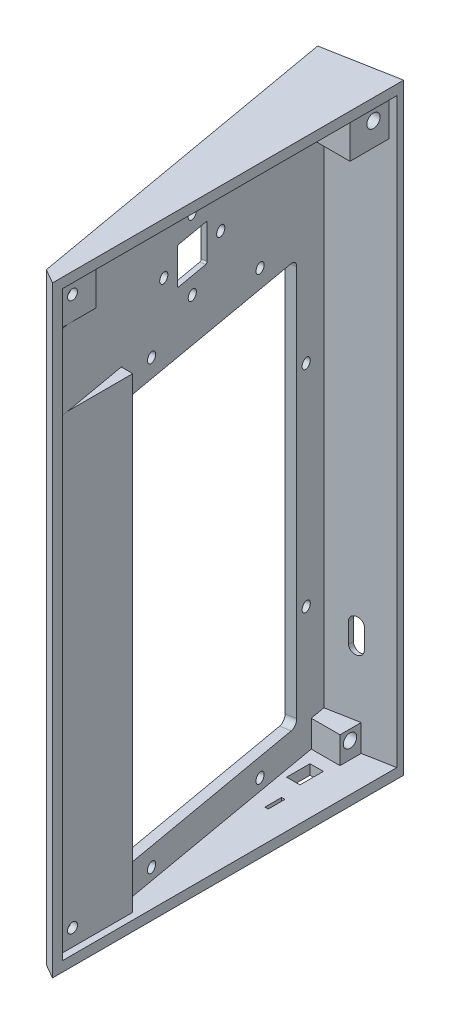
SolidWorks part; units mm, degrees
ref_plane "前视基准面" through (0, 0, 0) normal (0, 0, 1) x (1, 0, 0)
ref_plane "上视基准面" through (0, 0, 0) normal (0, 1, 0) x (1, 0, 0)
ref_plane "右视基准面" through (0, 0, 0) normal (1, 0, 0) x (0, 0, -1)
other "Configuration Table"
sketch "草图1" plane through (0, 0, 0) normal (0, 1, 0) x (1, 0, 0)
  line L0 (82.9035, -37.3993) -> (82.9035, -142.3993)
  line L1 (82.9035, -142.3993) -> (78.5734, -139.8993)
  line L2 (78.5734, -139.8993) -> (61.2086, -41.4185)
  line L3 (61.2086, -41.4185) -> (82.9035, -37.3993)
  dimension "D1" = 100
  dimension "D2" = 105
  dimension "D3" = 5
  dimension "D4" = 170
  dimension "D5" = 60
  dimension "D6" = 90.496
  dimension "D7" = 79.504
extrude "凸台-拉伸1" add sketch "草图1" along normal blind 180
sketch "草图5" plane through (52.2799, 0, -9.2184) normal (-0.9848, 0, 0.1736) x (0.1736, 0, 0.9848)
  line L0 (51.418, 180) -> (51.418, 0) construction
  line L1 (139.418, 12) -> (63.418, 12)
  line L2 (139.418, 12) -> (139.418, 133)
  line L3 (139.418, 133) -> (63.418, 133)
  line L4 (63.418, 12) -> (63.418, 133)
  line L5 (151.418, 180) -> (151.418, 0) construction
  line L6 (51.418, 0) -> (151.418, 0) construction
  dimension "D1" = 76
  dimension "D2" = 121
  dimension "D3" = 12
  dimension "D4" = 12
  dimension "D5" = 12
extrude "切除-拉伸2" cut sketch "草图5" against normal blind 2
sketch "草图7" plane through (82.9035, 0, 0) normal (1, 0, 0) x (0, 0, -1)
  line L8 (-139.3993, 3) -> (-40.3993, 3)
  line L9 (-40.3993, 3) -> (-40.3993, 177)
  line L10 (-40.3993, 177) -> (-139.3993, 177)
  line L11 (-139.3993, 177) -> (-139.3993, 3)
  line L12 (-139.3993, 3) -> (-40.3993, 3)
  line L13 (-40.3993, 3) -> (-40.3993, 177)
  line L14 (-40.3993, 177) -> (-139.3993, 177)
  line L15 (-139.3993, 177) -> (-139.3993, 3)
  dimension "D1" = 3
extrude "切除-拉伸3" cut sketch "草图7" against normal up to surface (19.8438 mm away) up to face at (71.8606, 72.5, 90.3116)
sketch "草图10" plane through (54.2496, 0, -9.5657) normal (0.9848, 0, -0.1736) x (-0.1736, 0, -0.9848)
  line L1 (-63.418, 12) -> (-59.918, 12) construction
  line L2 (-63.418, 12) -> (-63.418, 41) construction
  line L3 (-63.418, 41) -> (-59.918, 41) construction
  line L4 (-59.918, 12) -> (-59.918, 41) construction
  line L5 (-63.418, 133) -> (-59.918, 133) construction
  line L6 (-63.418, 133) -> (-63.418, 104) construction
  line L7 (-63.418, 104) -> (-59.918, 104) construction
  line L8 (-59.918, 133) -> (-59.918, 104) construction
  circle A0 centre (-59.918, 104) radius 1.5
  circle A1 centre (-59.918, 41) radius 1.5
  dimension "D1" = 29
  dimension "D2" = 29
  dimension "D3" = 3.5
  dimension "D4" = 3.5
extrude "切除-拉伸5" cut sketch "草图10" against normal blind 1
sketch "草图11" plane through (54.2496, 0, -9.5657) normal (0.9848, 0, -0.1736) x (-0.1736, 0, -0.9848)
  line L0 (-76.918, 6.5) -> (-116.918, 6.5) construction
  line L1 (-63.418, 133) -> (-76.918, 133) construction
  line L2 (-63.418, 133) -> (-63.418, 138.5) construction
  line L3 (-63.418, 138.5) -> (-76.918, 138.5) construction
  line L4 (-76.918, 133) -> (-76.918, 138.5) construction
  line L5 (-63.418, 12) -> (-76.918, 12) construction
  line L6 (-63.418, 12) -> (-63.418, 6.5) construction
  line L7 (-63.418, 6.5) -> (-76.918, 6.5) construction
  line L8 (-76.918, 12) -> (-76.918, 6.5) construction
  line L9 (-76.918, 138.5) -> (-116.918, 138.5) construction
  circle A0 centre (-116.918, 138.5) radius 1.5
  circle A1 centre (-76.918, 138.5) radius 1.5
  circle A2 centre (-116.918, 6.5) radius 1.5
  circle A3 centre (-76.918, 6.5) radius 1.5
  dimension "D1" = 13.5
  dimension "D2" = 5.5
  dimension "D3" = 13.5
  dimension "D4" = 5.5
  dimension "D5" = 40
  dimension "D6" = 40
extrude "切除-拉伸6" cut sketch "草图11" against normal blind 1
sketch "草图12" plane through (82.9035, 0, 0) normal (1, 0, 0) x (0, 0, -1)
  line L1 (-139.3993, 3) -> (-116.3993, 3)
  line L2 (-139.3993, 3) -> (-139.3993, 142.5)
  line L3 (-139.3993, 142.5) -> (-116.3993, 142.5)
  line L4 (-116.3993, 3) -> (-116.3993, 142.5)
  line L6 (-127.7343, 133) -> (-52.8889, 133) construction
  dimension "D1" = 9.5
  dimension "D2" = 23
extrude "凸台-拉伸3" add sketch "草图12" against normal up to surface (2.3874 mm away) up to face at (67.3458, 138.5, 64.7066)
sketch "草图13" plane through (54.2496, 0, -9.5657) normal (-0.9848, 0, 0.1736) x (0.1736, 0, 0.9848)
  line L4 (127.9081, 12) -> (139.418, 12)
  line L5 (139.418, 12) -> (139.418, 133)
  line L6 (139.418, 133) -> (127.9081, 133)
  line L7 (127.9081, 133) -> (127.9081, 12)
  line L8 (127.9081, 12) -> (139.418, 12)
  line L9 (139.418, 12) -> (139.418, 133)
  line L10 (139.418, 133) -> (127.9081, 133)
  line L11 (127.9081, 133) -> (127.9081, 12)
  dimension "D1" = 0
extrude "切除-拉伸7" cut sketch "草图13" against normal blind 2
sketch "草图14" plane through (52.2799, 0, -9.2184) normal (-0.9848, 0, 0.1736) x (0.1736, 0, 0.9848)
  line L0 (51.418, 180) -> (51.418, 0) construction
  line L1 (96.418, 151) -> (107.418, 151)
  line L2 (96.418, 151) -> (96.418, 162)
  line L3 (96.418, 162) -> (107.418, 162)
  line L4 (107.418, 151) -> (107.418, 162)
  line L5 (139.418, 133) -> (63.418, 133) construction
  line L6 (51.418, 180) -> (151.418, 180) construction
  dimension "D1" = 11
  dimension "D2" = 11
  dimension "D3" = 45
  dimension "D4" = 18
  dimension "D5" = 18
extrude "切除-拉伸8" cut sketch "草图14" against normal blind 2
sketch "草图17" plane through (9.4497, 0, 51.0074) normal (-0.1822, 0, -0.9833) x (-0.9833, 0, 0.1822)
  line L1 (-74.7037, 180) -> (-52.6396, 180)
  line L2 (-74.7037, 180) -> (-74.7037, 0)
  line L3 (-74.7037, 0) -> (-52.6396, 0)
  line L4 (-52.6396, 180) -> (-52.6396, 0)
extrude "凸台-拉伸9" add sketch "草图17" against normal blind 2
sketch "草图18" plane through (0, 0, 0) normal (0, -1, 0) x (1, 0, 0)
  line L0 (82.9035, 39.4333) -> (82.9035, 37.3993)
  line L1 (83.2679, 39.3658) -> (82.9035, 39.4333) construction
  line L2 (83.2679, 39.3658) -> (82.9035, 37.3993) construction
  line L3 (83.2679, 39.3658) -> (82.9035, 37.3993)
  line L4 (83.2679, 39.3658) -> (82.9035, 39.4333)
extrude "切除-拉伸9" cut sketch "草图18" against normal up to surface (180 mm away) up to face at (78.6267, 180, 73.3192)
sketch "草图19" plane through (0, 3, 0) normal (0, 1, 0) x (1, 0, 0)
  line L0 (82.9035, -40.3993) -> (82.9035, -36.7908) construction
  line L1 (77.596, -40.4166) -> (82.9035, -39.4333)
  line L2 (63.5225, -43.0238) -> (77.6894, -40.3993) construction
  line L3 (82.9035, -39.4333) -> (82.9035, -40.3993)
  line L4 (82.9035, -40.3993) -> (77.596, -40.4166)
extrude "切除-拉伸10" cut sketch "草图19" along normal up to surface (174 mm away) up to face at (77.507, 177, 80.5242)
sketch "草图20" plane through (82.9035, 0, 0) normal (1, 0, 0) x (0, 0, -1)
  line L1 (-139.3993, 142.5) -> (-116.3993, 142.5)
  line L2 (-139.3993, 142.5) -> (-139.3993, 3)
  line L3 (-139.3993, 3) -> (-116.3993, 3)
  line L4 (-116.3993, 142.5) -> (-116.3993, 3)
extrude "切除-拉伸11" cut sketch "草图20" against normal blind 2
sketch "草图21" plane through (54.2496, 0, -9.5657) normal (0.9848, 0, -0.1736) x (-0.1736, 0, -0.9848)
  line L0 (-107.418, 156.5) -> (-112.418, 156.5) construction
  line L1 (-107.418, 151) -> (-107.418, 162) construction
  line L2 (-101.918, 162) -> (-101.918, 167) construction
  line L3 (-107.418, 162) -> (-96.418, 162) construction
  line L4 (-96.418, 156.5) -> (-91.418, 156.5) construction
  line L5 (-96.418, 162) -> (-96.418, 151) construction
  line L6 (-101.918, 151) -> (-101.918, 146) construction
  line L7 (-96.418, 151) -> (-107.418, 151) construction
  circle A0 centre (-112.418, 156.5) radius 1.5
  circle A1 centre (-91.418, 156.5) radius 1.5
  circle A2 centre (-101.918, 146) radius 1.5
  circle A3 centre (-101.918, 167) radius 1.5
  dimension "D1" = 5
extrude "切除-拉伸12" cut sketch "草图21" against normal blind 1
sketch "草图23" plane through (80.9035, 0, 0) normal (1, 0, 0) x (0, 0, -1)
  line L0 (-51.4333, 8) -> (-51.4333, 26.4031) construction
  line L1 (-139.3993, 3) -> (-127.3993, 3)
  line L2 (-139.3993, 3) -> (-139.3993, 15)
  line L3 (-139.3993, 15) -> (-127.3993, 15)
  line L4 (-127.3993, 3) -> (-127.3993, 15)
  line L5 (-39.4333, 177) -> (-139.3993, 177) construction
  line L11 (-51.4333, 165) -> (-39.4333, 165)
  line L12 (-51.4333, 165) -> (-51.4333, 177)
  line L13 (-51.4333, 177) -> (-39.4333, 177)
  line L14 (-39.4333, 165) -> (-39.4333, 177)
  line L15 (-127.3993, 8) -> (-127.3993, 23.4787) construction
  line L17 (-127.3993, 165) -> (-139.3993, 165)
  line L18 (-127.3993, 165) -> (-127.3993, 177)
  line L19 (-127.3993, 177) -> (-139.3993, 177)
  line L20 (-139.3993, 165) -> (-139.3993, 177)
  dimension "D1" = 12
  dimension "D2" = 12
  dimension "D5" = 0
  dimension "D6" = 12
  dimension "D7" = 12
  dimension "D8" = 12
  dimension "D9" = 12
  dimension "D11" = 0
extrude "凸台-拉伸10" add sketch "草图23" against normal up to surface (0.3874 mm away) up to face at (73.5103, 156.5, 99.6673)
fillet "圆角4" radius 2 5 edges at (64.2772, 133, 53.0625) (78.4592, 133, 127.7343) (64.2772, 12, 53.0625) (77.4744, 12, 127.9079) (80.394, 12, 127.3931)
sketch "草图26" plane through (0, 177, 0) normal (0, 1, 0) x (1, 0, 0)
  line L3 (63.1752, -41.0542) -> (71.9242, -39.4333)
  line L4 (71.9242, -39.4333) -> (62.8894, -39.4333)
  line L5 (62.8894, -39.4333) -> (63.1752, -41.0542)
  line L6 (63.1752, -41.0542) -> (71.9242, -39.4333)
  line L7 (71.9242, -39.4333) -> (62.8894, -39.4333)
  line L8 (62.8894, -39.4333) -> (63.1752, -41.0542)
  dimension "D1" = 0
extrude "切除-拉伸15" cut sketch "草图26" against normal up to next
sketch "草图27" plane through (82.9035, 0, 0) normal (1, 0, 0) x (0, 0, -1)
  line L1 (-39.4333, 3) -> (-47.4333, 3)
  line L2 (-39.4333, 3) -> (-39.4333, 11)
  line L3 (-39.4333, 11) -> (-47.4333, 11)
  line L4 (-47.4333, 3) -> (-47.4333, 11)
  dimension "D1" = 8
  dimension "D2" = 8
extrude "凸台-拉伸11" add sketch "草图27" against normal up to surface (18.6035 mm away) up to face at (73.5103, 156.5, 99.6673)
sketch "草图28" plane through (82.9035, 0, 0) normal (1, 0, 0) x (0, 0, -1)
  line L1 (-47.4333, 3) -> (-39.4333, 3)
  line L2 (-47.4333, 3) -> (-47.4333, 11)
  line L3 (-47.4333, 11) -> (-39.4333, 11)
  line L4 (-39.4333, 3) -> (-39.4333, 11)
extrude "切除-拉伸16" cut sketch "草图28" against normal blind 9
sketch "草图29" plane through (0, 11, 0) normal (0, -1, 0) x (1, 0, 0)
  line L3 (73.9035, 41.1006) -> (73.9035, 39.4333)
  line L4 (73.9035, 39.4333) -> (82.9035, 39.4333)
  line L5 (82.9035, 39.4333) -> (73.9035, 41.1006)
  line L6 (73.9035, 41.1006) -> (73.9035, 39.4333)
  line L7 (73.9035, 39.4333) -> (82.9035, 39.4333)
  line L11 (82.9035, 39.4333) -> (73.9035, 41.1006)
  dimension "D1" = 0
extrude "凸台-拉伸12" add sketch "草图29" along normal up to surface (8 mm away) up to face at (77.0227, 3, 85.6663)
sketch "草图30" plane through (0, 3, 0) normal (0, -1, 0) x (1, 0, 0)
  line L3 (71.9242, 39.4333) -> (63.1752, 41.0542)
  line L4 (63.1752, 41.0542) -> (62.8894, 39.4333)
  line L5 (62.8894, 39.4333) -> (71.9242, 39.4333)
  line L6 (71.9242, 39.4333) -> (63.1752, 41.0542)
  line L7 (63.1752, 41.0542) -> (62.8894, 39.4333)
  line L8 (62.8894, 39.4333) -> (71.9242, 39.4333)
  dimension "D1" = 0
extrude "切除-拉伸17" cut sketch "草图30" against normal up to next
sketch "草图31" plane through (0, 0, 0) normal (0, -1, 0) x (1, 0, 0)
  line L1 (82.9035, 37.3993) -> (68.9035, 37.3993) construction
  line L2 (82.9035, 37.3993) -> (82.9035, 51.3993) construction
  line L3 (82.9035, 51.3993) -> (68.9035, 51.3993) construction
  line L4 (68.9035, 37.3993) -> (68.9035, 51.3993) construction
  line L5 (68.9035, 51.3993) -> (72.9035, 51.3993)
  line L6 (68.9035, 51.3993) -> (68.9035, 58.3993)
  line L7 (68.9035, 58.3993) -> (72.9035, 58.3993)
  line L8 (72.9035, 51.3993) -> (72.9035, 58.3993)
  dimension "D1" = 14
  dimension "D2" = 14
  dimension "D3" = 7
  dimension "D4" = 4
extrude "切除-拉伸18" cut sketch "草图31" against normal up to next
ref_plane "基准面1" through (0, 0, 37.3993) normal (0, 0, -1) x (-1, 0, 0)
ref_plane "基准面2" through (0, 0, 39.7193) normal (0, 0, -1) x (-1, 0, 0)
sketch "草图32" plane through (0, 0, 39.7193) normal (0, 0, -1) x (-1, 0, 0)
  line L0 (-72.7086, 36) -> (-72.7086, 30) construction
  line L1 (-70.7086, 36) -> (-70.7086, 30)
  line L2 (-74.7086, 36) -> (-74.7086, 30)
  line L3 (-82.9035, 180) -> (-61.2086, 180) construction
  line L4 (-61.2086, 180) -> (-61.2086, 0) construction
  arc A0 (-70.7086, 36) -> (-74.7086, 36) centre (-72.7086, 36) ccw
  arc A1 (-74.7086, 30) -> (-70.7086, 30) centre (-72.7086, 30) ccw
  point P2 (-72.7086, 33)
  point P9 (-72.7086, 28)
  point P10 (-72.7086, 38)
  dimension "D1" = 147
  dimension "D2" = 10
  dimension "D3" = 4
  dimension "D4" = 9.5
extrude "切除-拉伸23" cut sketch "草图32" against normal up to surface (1.9733 mm away) up to face at (75.3083, 89, 40.8404)
ref_plane "基准面4" through (0, 0, 40.2193) normal (0, 0, -1) x (-1, 0, 0)
sketch "草图35" plane through (0, 0, 40.2193) normal (0, 0, -1) x (-1, 0, 0)
  line L0 (-74.7086, 36) -> (-74.7086, 30) construction
  line L1 (-76.7086, 41) -> (-68.7086, 41)
  line L2 (-76.7086, 41) -> (-76.7086, 25)
  line L3 (-76.7086, 25) -> (-68.7086, 25)
  line L4 (-68.7086, 41) -> (-68.7086, 25)
  line L5 (-70.7086, 30) -> (-70.7086, 36) construction
  arc A0 (-70.7086, 36) -> (-74.7086, 36) centre (-72.7086, 36) ccw construction
  arc A1 (-74.7086, 30) -> (-70.7086, 30) centre (-72.7086, 30) ccw construction
  dimension "D1" = 5
  dimension "D2" = 5
  dimension "D3" = 2
  dimension "D4" = 2
extrude "切除-拉伸25" cut sketch "草图35" along normal up to surface (0.1902 mm away) up to face at (72.0561, 90, 39.4089)
fillet "圆角5" radius 0.5 4 edges at (76.7086, 25, 39.3831) (76.7086, 41, 39.3831) (68.7086, 25, 40.1241) (68.7086, 41, 40.1241)
sketch "草图36" plane through (0, 0, 0) normal (0, -1, 0) x (1, 0, 0)
  line L1 (82.9035, 37.3993) -> (74.4035, 37.3993) construction
  line L2 (82.9035, 37.3993) -> (82.9035, 64.3993) construction
  line L3 (82.9035, 64.3993) -> (74.4035, 64.3993) construction
  line L4 (74.4035, 37.3993) -> (74.4035, 64.3993) construction
  line L5 (74.4035, 64.3993) -> (73.4035, 64.3993)
  line L6 (74.4035, 64.3993) -> (74.4035, 69.3993)
  line L7 (74.4035, 69.3993) -> (73.4035, 69.3993)
  line L8 (73.4035, 64.3993) -> (73.4035, 69.3993)
  dimension "D1" = 8.5
  dimension "D2" = 27
  dimension "D3" = 1
  dimension "D4" = 5
extrude "切除-拉伸26" cut sketch "草图36" against normal up to next
sketch "草图37" plane through (0, 0, 0) normal (0, -1, 0) x (1, 0, 0)
  line L0 (73.4035, 66.8993) -> (74.4035, 66.8993) construction
  line L1 (73.4035, 69.3993) -> (73.4035, 64.3993) construction
  line L2 (74.4035, 64.3993) -> (74.4035, 69.3993) construction
  line L3 (73.9035, 64.3993) -> (73.9035, 69.3993) construction
  line L4 (73.4035, 64.3993) -> (74.4035, 64.3993) construction
  line L5 (74.4035, 69.3993) -> (73.4035, 69.3993) construction
  line L7 (74.9035, 69.8993) -> (72.9035, 69.8993)
  line L8 (74.9035, 69.8993) -> (74.9035, 63.8993)
  line L9 (74.9035, 63.8993) -> (72.9035, 63.8993)
  line L10 (72.9035, 69.8993) -> (72.9035, 63.8993)
  line L11 (74.9035, 69.8993) -> (72.9035, 63.8993) construction
  line L12 (74.9035, 63.8993) -> (72.9035, 69.8993) construction
  point P12 (73.9035, 66.8993)
  dimension "D1" = 6
  dimension "D2" = 2
extrude "切除-拉伸27" cut sketch "草图37" against normal blind 1
sketch "草图38" plane through (73.9035, 0, 0) normal (1, 0, 0) x (0, 0, -1)
  line L0 (-47.4333, 3) -> (-41.1006, 3) construction
  line L1 (-47.4333, 11) -> (-44.4333, 11) construction
  line L2 (-47.4333, 11) -> (-47.4333, 8) construction
  line L3 (-47.4333, 8) -> (-44.4333, 8) construction
  line L4 (-44.4333, 11) -> (-44.4333, 8) construction
  line L5 (-47.4333, 11) -> (-47.4333, 3) construction
  circle A0 centre (-44.4333, 8) radius 2
  dimension "D1" = 5
  dimension "D2" = 3
extrude "切除-拉伸28" cut sketch "草图38" against normal blind 3 contours A0
sketch "草图39" plane through (80.9035, 0, 0) normal (1, 0, 0) x (0, 0, -1)
  line L0 (-47.4333, 10.1358) -> (-47.4333, 2.8866) construction
  line L4 (-39.8038, 177) -> (-51.4333, 177) construction
  line L5 (-47.4333, 169) -> (-39.8038, 169) construction
  line L6 (-47.4333, 169) -> (-47.4333, 177) construction
  line L7 (-47.4333, 177) -> (-39.8038, 177) construction
  line L8 (-39.8038, 169) -> (-39.8038, 177) construction
  line L10 (-47.4333, 169) -> (-44.4333, 169) construction
  line L11 (-47.4333, 169) -> (-47.4333, 172) construction
  line L12 (-47.4333, 172) -> (-44.4333, 172) construction
  line L13 (-44.4333, 169) -> (-44.4333, 172) construction
  circle A0 centre (-44.4333, 172) radius 2
  dimension "D1" = 8
  dimension "D2" = 3
  dimension "D3" = 3
extrude "切除-拉伸30" cut sketch "草图39" against normal blind 3
sketch "草图40" plane through (80.9035, 0, 0) normal (1, 0, 0) x (0, 0, -1)
  line L1 (-127.3993, 177) -> (-131.3993, 177) construction
  line L2 (-127.3993, 177) -> (-127.3993, 171) construction
  line L3 (-127.3993, 171) -> (-131.3993, 171) construction
  line L4 (-131.3993, 177) -> (-131.3993, 171) construction
  line L5 (-131.3993, 171) -> (-134.3993, 171) construction
  line L6 (-131.3993, 171) -> (-131.3993, 172) construction
  line L7 (-131.3993, 172) -> (-134.3993, 172) construction
  line L8 (-134.3993, 171) -> (-134.3993, 172) construction
  line L9 (-139.3993, 3) -> (-134.3993, 3) construction
  line L10 (-139.3993, 3) -> (-139.3993, 8) construction
  line L11 (-139.3993, 8) -> (-134.3993, 8) construction
  line L12 (-134.3993, 3) -> (-134.3993, 8) construction
  circle A0 centre (-134.3993, 172) radius 1.5
  circle A1 centre (-134.3993, 8) radius 1.5
  dimension "D5" = 5
  dimension "D1" = 6
  dimension "D2" = 4
  dimension "D3" = 3
  dimension "D4" = 1
  dimension "D6" = 5
extrude "切除-拉伸31" cut sketch "草图40" against normal blind 2
sketch "草图42" plane through (54.2496, 0, -9.5657) normal (-0.9848, 0, 0.1736) x (0.1736, 0, 0.9848)
  line L3 (139.0778, 15) -> (139.0778, 12.8842)
  line L4 (139.418, 14) -> (139.418, 15)
  line L5 (139.418, 15) -> (139.0778, 15)
  line L6 (139.0778, 15) -> (139.0778, 12.8842)
  line L7 (139.418, 14) -> (139.418, 15)
  line L8 (139.418, 15) -> (139.0778, 15)
  arc A1 (139.0778, 12.8842) -> (139.418, 14) centre (137.418, 14) ccw
  arc A2 (139.0778, 12.8842) -> (139.418, 14) centre (137.418, 14) ccw
  dimension "D1" = 0
extrude "切除-拉伸34" cut sketch "草图42" against normal up to surface (2 mm away) up to face at (79.6913, 72.5, 123.2038)
chamfer "倒角2" distance 2.5 angle 30 4 edges at (69.0228, 156.5, 85.7348) (69.9778, 151, 91.1513) (69.9778, 162, 91.1513) (70.9329, 156.5, 96.5677) first distance on face at (69.9778, 156.5, 91.1513)
fillet "圆角6" radius 0.5 4 edges at (70.7183, 151, 85.4359) (72.6284, 151, 96.2688) (72.6284, 162, 96.2688) (70.7183, 162, 85.4359)
sketch "草图48" plane through (54.2496, 0, -9.5657) normal (0.9848, 0, -0.1736) x (-0.1736, 0, -0.9848)
  line L0 (-96.918, 151) -> (-106.918, 151) construction
  line L1 (-106.918, 162) -> (-96.918, 162) construction
  line L2 (-107.418, 151.5) -> (-107.418, 161.5) construction
  line L3 (-96.418, 161.5) -> (-96.418, 151.5) construction
  line L4 (-96.918, 151) -> (-106.918, 151)
  line L5 (-106.918, 162) -> (-96.918, 162)
  line L6 (-107.418, 151.5) -> (-107.418, 161.5)
  line L7 (-96.418, 161.5) -> (-96.418, 151.5)
  line L16 (-57.8783, 3) -> (-57.8783, 11)
  line L17 (-57.8783, 11) -> (-53.4008, 11)
  line L18 (-53.4008, 11) -> (-53.4008, 165)
  line L19 (-53.4008, 165) -> (-61.94, 165)
  line L20 (-61.94, 165) -> (-61.94, 177)
  line L21 (-61.94, 177) -> (-139.0778, 177)
  line L22 (-139.0778, 177) -> (-139.0778, 165)
  line L23 (-139.0778, 165) -> (-151.2629, 165)
  line L24 (-151.2629, 165) -> (-151.2629, 142.5)
  line L25 (-151.2629, 142.5) -> (-127.9081, 142.5)
  line L26 (-127.9081, 142.5) -> (-127.9081, 133)
  line L27 (-127.9081, 133) -> (-65.418, 133)
  line L28 (-63.418, 131) -> (-63.418, 14)
  line L29 (-65.418, 12) -> (-127.9081, 12)
  line L30 (-127.9081, 12) -> (-127.9081, 3)
  line L31 (-127.9081, 3) -> (-57.8783, 3)
  line L32 (-57.8783, 3) -> (-57.8783, 11)
  line L33 (-57.8783, 11) -> (-53.4008, 11)
  line L34 (-53.4008, 11) -> (-53.4008, 165)
  line L35 (-53.4008, 165) -> (-61.94, 165)
  line L36 (-61.94, 165) -> (-61.94, 177)
  line L37 (-61.94, 177) -> (-139.0778, 177)
  line L38 (-139.0778, 177) -> (-139.0778, 165)
  line L39 (-139.0778, 165) -> (-151.2629, 165)
  line L40 (-151.2629, 165) -> (-151.2629, 142.5)
  line L41 (-151.2629, 142.5) -> (-127.9081, 142.5)
  line L42 (-127.9081, 142.5) -> (-127.9081, 133)
  line L43 (-127.9081, 133) -> (-65.418, 133)
  line L44 (-63.418, 131) -> (-63.418, 14)
  line L45 (-65.418, 12) -> (-127.9081, 12)
  line L46 (-127.9081, 12) -> (-127.9081, 3)
  line L47 (-127.9081, 3) -> (-57.8783, 3)
  circle A0 centre (-116.918, 6.5) radius 1.5 construction
  circle A1 centre (-76.918, 6.5) radius 1.5 construction
  arc A2 (-63.418, 131) -> (-65.418, 133) centre (-65.418, 131) ccw
  arc A3 (-65.418, 12) -> (-63.418, 14) centre (-65.418, 14) ccw
  arc A4 (-63.418, 131) -> (-65.418, 133) centre (-65.418, 131) ccw
  arc A5 (-65.418, 12) -> (-63.418, 14) centre (-65.418, 14) ccw
  circle A6 centre (-59.918, 41) radius 1.5 construction
  circle A7 centre (-59.918, 104) radius 1.5 construction
  circle A8 centre (-76.918, 138.5) radius 1.5 construction
  circle A9 centre (-116.918, 138.5) radius 1.5 construction
  circle A10 centre (-101.918, 146) radius 1.5 construction
  circle A11 centre (-91.418, 156.5) radius 1.5 construction
  circle A12 centre (-112.418, 156.5) radius 1.5 construction
  arc A13 (-107.418, 151.5) -> (-106.918, 151) centre (-106.918, 151.5) ccw construction
  arc A14 (-96.918, 151) -> (-96.418, 151.5) centre (-96.918, 151.5) ccw construction
  arc A15 (-106.918, 162) -> (-107.418, 161.5) centre (-106.918, 161.5) ccw construction
  circle A16 centre (-101.918, 167) radius 1.5 construction
  circle A17 centre (-116.918, 6.5) radius 1.5
  circle A18 centre (-76.918, 6.5) radius 1.5
  circle A19 centre (-59.918, 41) radius 1.5
  circle A20 centre (-59.918, 104) radius 1.5
  circle A21 centre (-76.918, 138.5) radius 1.5
  circle A22 centre (-116.918, 138.5) radius 1.5
  circle A23 centre (-101.918, 146) radius 1.5
  circle A24 centre (-91.418, 156.5) radius 1.5
  circle A25 centre (-112.418, 156.5) radius 1.5
  arc A26 (-107.418, 151.5) -> (-106.918, 151) centre (-106.918, 151.5) ccw
  arc A27 (-96.918, 151) -> (-96.418, 151.5) centre (-96.918, 151.5) ccw
  arc A28 (-106.918, 162) -> (-107.418, 161.5) centre (-106.918, 161.5) ccw
  circle A29 centre (-101.918, 167) radius 1.5
  arc A30 (-96.418, 161.5) -> (-96.918, 162) centre (-96.918, 161.5) ccw construction
  arc A31 (-96.418, 161.5) -> (-96.918, 162) centre (-96.918, 161.5) ccw
  dimension "D1" = 0
extrude "凸台-拉伸15" add sketch "草图48" along normal blind 1
